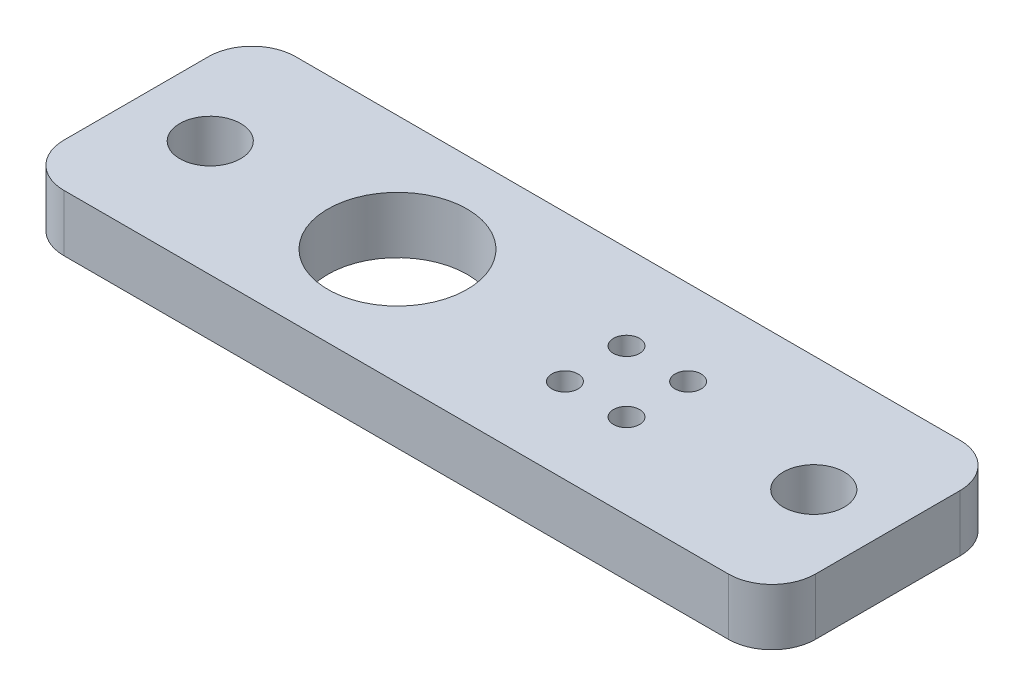
SolidWorks part; units mm, degrees
ref_plane "Front Plane" through (0, 0, 0) normal (0, 0, 1) x (1, 0, 0)
ref_plane "Top Plane" through (0, 0, 0) normal (0, 1, 0) x (1, 0, 0)
ref_plane "Right Plane" through (0, 0, 0) normal (1, 0, 0) x (0, 0, -1)
sketch "Sketch1" plane through (0, 0, 0) normal (0, 1, 0) x (1, 0, 0)
  line L0 (21.5, 0) -> (-47.8, 0) construction
  line L1 (-56.3, 13.3) -> (30, 13.3)
  line L2 (-56.3, 13.3) -> (-56.3, -13.3)
  line L3 (-56.3, -13.3) -> (30, -13.3)
  line L4 (30, 13.3) -> (30, -13.3)
  line L5 (-26.3, 0) -> (0, 0) construction
  circle A0 centre (0, 0) radius 8.3 construction
  circle A1 centre (-47.8, 0) radius 3.5
  circle A2 centre (21.5, 0) radius 3.5
  circle A3 centre (-26.3, 0) radius 8
  point P11 (-13.15, 0)
  point P12 (-13.15, 0)
  point P13 (-13.15, 13.3)
  point P14 (-56.3, 0)
  dimension "D1" = 10
  dimension "syringe top" = 16.6
  dimension "D2" = 7
  dimension "Motor " = 16
  dimension "D3" = 10
  dimension "D4" = 5
  dimension "D5" = 5
extrude "Boss-Extrude1" add sketch "Sketch1" along normal blind 6.5
sketch "Sketch2" plane through (0, 0, 0) normal (0, -1, 0) x (1, 0, 0)
  circle A0 centre (0, 0) radius 8.3 construction
  circle A1 centre (0, 0) radius 8.3
extrude "Cut-Extrude1" cut sketch "Sketch2" against normal blind 2
fillet "Fillet1" radius 5 4 edges at (-56.3, 3.25, -13.3) (30, 3.25, -13.3) (30, 3.25, 13.3) (-56.3, 3.25, 13.3)
sketch "Sketch3" plane through (0, 2, 0) normal (0, -1, 0) x (1, 0, 0)
  line L0 (0, 0) -> (0, 8.3) construction
  line L1 (0, 0) -> (3.5355, 3.5355) construction
  circle A0 centre (3.5355, 3.5355) radius 1.5
  circle A2 centre (0, 0) radius 8.3 construction
  point P0 (0, 4.9661)
  point P6 (0, 5.3329)
  point P7 (3.5668, 3.0497)
  dimension "D1" = 3
  dimension "D2" = 45
  dimension "D3" = 5
extrude "Cut-Extrude2" cut sketch "Sketch3" against normal up to next
pattern_circular "CirPattern1" count 4 over 360 about axis through (0, 2, 0) along (0, -1, 0) of "Cut-Extrude2"
